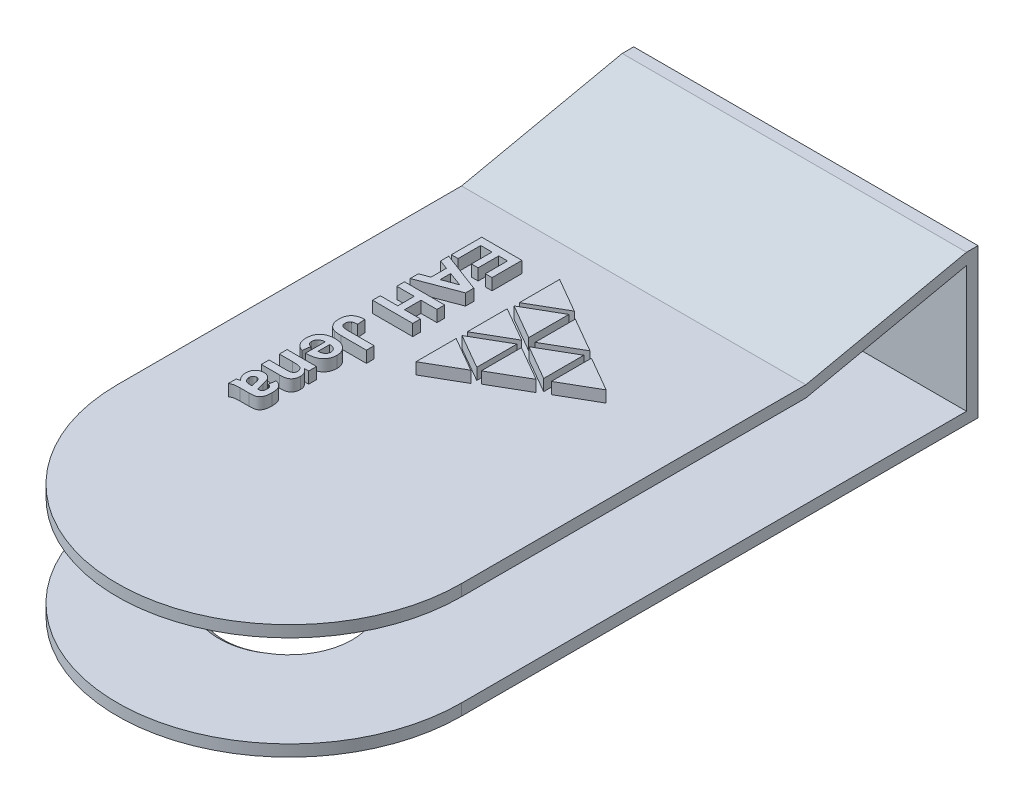
SolidWorks part; units mm, degrees
ref_plane "Ebene vorne" through (0, 0, 0) normal (0, 0, 1) x (1, 0, 0)
ref_plane "Ebene oben" through (0, 0, 0) normal (0, 1, 0) x (1, 0, 0)
ref_plane "Ebene rechts" through (0, 0, 0) normal (1, 0, 0) x (0, 0, -1)
sketch "Skizze1" plane through (0, 0, 0) normal (0, 1, 0) x (1, 0, 0)
  line L1 (15, -22.5) -> (-15, -22.5)
  line L2 (15, -22.5) -> (15, 22.5)
  line L3 (15, 22.5) -> (-15, 22.5)
  line L4 (-15, -22.5) -> (-15, 22.5)
  line L5 (15, -22.5) -> (-15, 22.5) construction
  line L6 (15, 22.5) -> (-15, -22.5) construction
  arc A0 (15, -22.5) -> (-15, -22.5) centre (0, -22.5) cw
  point P0 (0, 0)
  dimension "D1" = 30
  dimension "D2" = 45
extrude "Aufsatz-Linear austragen1" add sketch "Skizze1" along normal blind 1 contours L4 L1 L2 L3 | A0 L1 region at (0, 0, 28.8662) region at (0, 0, 0)
sketch "Skizze2" plane through (0, 1, 0) normal (0, 1, 0) x (1, 0, 0)
  line L0 (15, -22.5) -> (15, 22.5) construction
  line L1 (-15, 22.5) -> (15, 22.5)
  line L2 (-15, 22.5) -> (-15, 21.5)
  line L3 (-15, 21.5) -> (15, 21.5)
  line L4 (15, 22.5) -> (15, 21.5)
  dimension "D1" = 1
extrude "Aufsatz-Linear austragen2" add sketch "Skizze2" along normal blind 11
ref_plane "Ebene1" through (0, 9, 0) normal (0, 1, 0) x (1, 0, 0)
sketch "Skizze3" plane through (0, 9, 0) normal (0, 1, 0) x (1, 0, 0)
  line L0 (15, -22.5) -> (15, 21.5) construction
  line L1 (-15, -22.5) -> (15, -22.5)
  line L2 (-15, -22.5) -> (-15, 7.5)
  line L3 (-15, 7.5) -> (15, 7.5)
  line L4 (15, -22.5) -> (15, 7.5)
  arc A0 (15, -22.5) -> (-15, -22.5) centre (0, -22.5) cw
  dimension "D1" = 30
extrude "Aufsatz-Linear austragen3" add sketch "Skizze3" along normal blind 1 separate body contours L1 L4 L3 L2 | A0 L1 region at (0, 9, 7.5) region at (0, 9, 28.8662)
ref_plane "Ebene2" through (15, 0, 0) normal (1, 0, 0) x (0, 0, -1)
sketch "Skizze5" plane through (15, 0, 0) normal (1, 0, 0) x (0, 0, -1)
  line L0 (7.5, 9) -> (21.5, 12)
  line L1 (21.5, 12) -> (22.5, 12)
  line L2 (22.5, 12) -> (22.5, 13)
  line L3 (22.5, 13) -> (21.5, 13)
  line L4 (21.5, 13) -> (7.5, 10)
  line L5 (7.5, 10) -> (7.5, 9)
  dimension "D1" = 1
extrude "Aufsatz-Linear austragen4" add sketch "Skizze5" against normal blind 30
sketch "Skizze6" plane through (0, 0, 0) normal (0, -1, 0) x (1, 0, 0)
  circle A0 centre (0, 22.5) radius 8
extrude "Aufsatz-Linear austragen5" add sketch "Skizze6" along normal blind 1
sketch "Skizze7" plane through (0, -1, 0) normal (0, -1, 0) x (-1, 0, 0)
  circle A0 centre (0, -22.5) radius 6.3
extrude "Schnitt-Linear austragen1" cut sketch "Skizze7" against normal blind 2
thread "Gewinde1" pitch 1.5 method extrude profile "Gewindeprofil1" start angle 0, offset 1.6, length 4, pitch 1.5, diameter 12.6
ref_plane "Ebene3" through (6.3, -2.6, 22.5) normal (0, 0, 1) x (1, 0, 0)
sketch "Gewindeprofil1" plane through (6.3, -2.6, 22.5) normal (0, 0, 1) x (1, 0, 0)
  line L0 (0, 0) -> (0, 1.5) construction
  line L11 (0, 0) -> (0, 1.3125)
  line L12 (0, 1.3125) -> (-0.8119, 0.8437)
  line L13 (-0.8119, 0.8437) -> (-0.8119, 0.4687)
  line L15 (-0.8119, 0.4687) -> (0, 0)
  line L17 (-0.8119, 0.6562) -> (0, 0.6562) construction
  point P2 (0, 0)
  dimension "Pitch" = 1.5
  dimension "Profile_Angle" = 60
  dimension "Profile_Land" = 0.375
  dimension "Profile_Height" = 0.8119
sketch "Skizze10" plane through (0, -1, 0) normal (0, -1, 0) x (1, 0, 0)
  circle A0 centre (0, 22.5) radius 12.6328
extrude "Schnitt-Linear austragen2" cut sketch "Skizze10" along normal blind 5
sketch "Skizze11" plane through (0, 1, 0) normal (0, 1, 0) x (1, 0, 0)
  circle A0 centre (0.3145, -22.5) radius 16.474
extrude "Schnitt-Linear austragen3" cut sketch "Skizze11" along normal blind 5
sketch "Skizze12" plane through (0, 10, 0) normal (0, 1, 0) x (1, 0, 0)
  line L0 (-2.6753, 3.7189) -> (-2.6753, 0.2189)
  line L1 (-2.6753, 0.2189) -> (0.3558, 1.9689)
  line L2 (0.3558, 1.9689) -> (-2.6753, 3.7189)
  line L3 (-2.7489, -0.7784) -> (-2.7489, -4.247)
  line L4 (-2.7489, -4.247) -> (0.255, -2.5127)
  line L5 (0.255, -2.5127) -> (-2.7489, -0.7784)
  line L8 (-2.7244, -5.247) -> (-2.7244, -8.747)
  line L9 (-2.7244, -8.747) -> (0.3067, -6.997)
  line L10 (0.3067, -6.997) -> (-2.7244, -5.247)
  line L11 (1.0034, 1.4065) -> (1.0034, -2.0935)
  line L12 (1.0034, -2.0935) -> (4.0345, -0.3435)
  line L13 (4.0345, -0.3435) -> (1.0034, 1.4065)
  line L14 (0.8099, -3.0923) -> (0.8099, -6.5923)
  line L15 (0.8099, -6.5923) -> (3.841, -4.8423)
  line L16 (3.841, -4.8423) -> (0.8099, -3.0923)
  line L17 (4.6566, -0.8375) -> (4.6566, -4.3375)
  line L18 (4.6566, -4.3375) -> (7.6877, -2.5875)
  line L19 (7.6877, -2.5875) -> (4.6566, -0.8375)
  line L20 (4.1004, -0.9453) -> (4.1004, -4.4453)
  line L23 (1.0693, -2.6953) -> (4.1004, -0.9453)
  line L24 (4.1004, -4.4453) -> (1.0693, -2.6953)
  line L25 (0.3684, 1.484) -> (0.3684, -2.016)
  line L26 (-2.6627, -0.266) -> (0.3684, 1.484)
  line L27 (0.3684, -2.016) -> (-2.6627, -0.266)
  line L28 (0.3415, -3.0158) -> (0.3415, -6.5158)
  line L29 (-2.6896, -4.7658) -> (0.3415, -3.0158)
  line L30 (0.3415, -6.5158) -> (-2.6896, -4.7658)
  dimension "D1" = 3.5
  dimension "D2" = 3.5
  dimension "D3" = 3.5
  dimension "D4" = 1
  dimension "D5" = 1
sketch "Skizze13" plane through (0, 10, 0) normal (0, 1, 0) x (1, 0, 0)
  text T0 "\r\n\r\n\r\n\r\nEAH Jena" font "Arial" height 3.5
extrude "Aufsatz-Linear austragen6" add sketch "Skizze13" along normal blind 1
extrude "Aufsatz-Linear austragen7" add sketch "Skizze12" along normal blind 1
